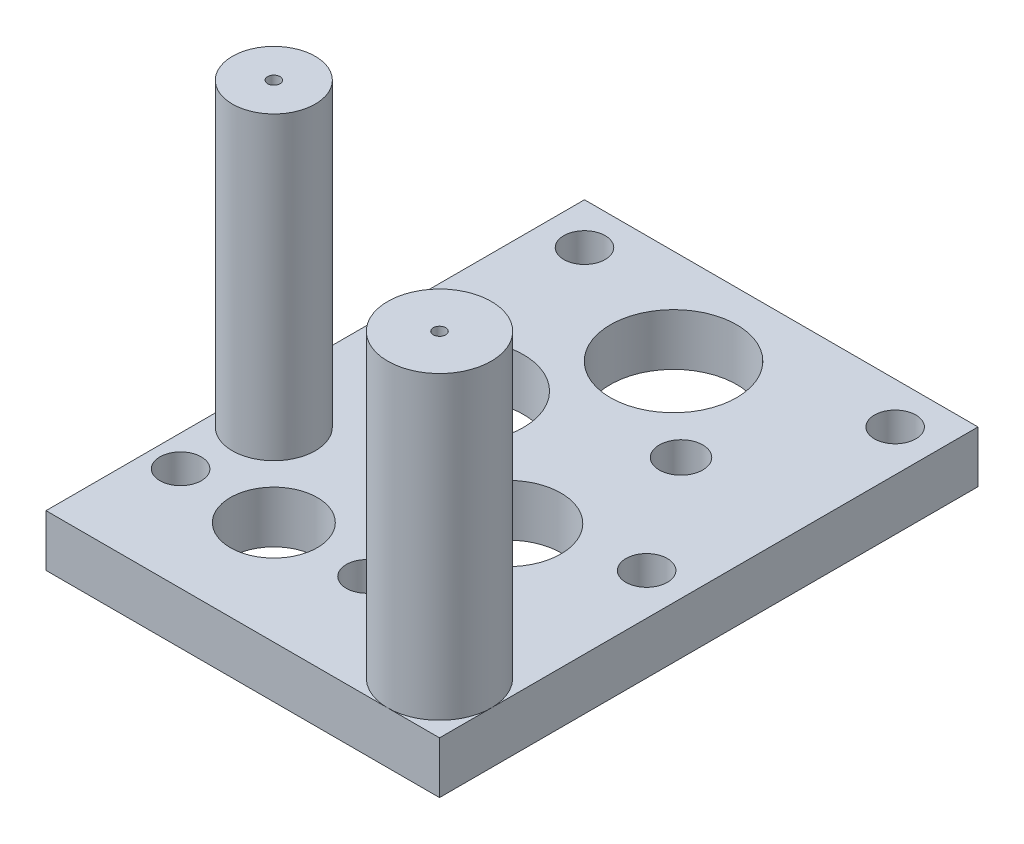
SolidWorks part; units mm, degrees
ref_plane "前视基准面" through (0, 0, 0) normal (0, 0, 1) x (1, 0, 0)
ref_plane "上视基准面" through (0, 0, 0) normal (0, 1, 0) x (1, 0, 0)
ref_plane "右视基准面" through (0, 0, 0) normal (1, 0, 0) x (0, 0, -1)
other "Configuration Table"
sketch "草图1" plane through (0, 0, 0) normal (0, 1, 0) x (1, 0, 0)
  line L1 (-5, 11) -> (14, 11)
  line L2 (-5, 11) -> (-5, -15)
  line L3 (-5, -15) -> (14, -15)
  line L4 (14, 11) -> (14, -15)
  circle A0 centre (0, 0) radius 3.05
  circle A3 centre (8.1071, 2.5542) radius 1.05
  circle A4 centre (3.9, 6.4) radius 3.05
  circle A5 centre (1, -10) radius 2.1
  circle A6 centre (6.6941, -4.3806) radius 2.55
  circle A7 centre (-3.5, -10) radius 1
  circle A8 centre (5.5, -10) radius 1
  circle A10 centre (-3.5, -10) radius 0.8
  circle A11 centre (5.5, -10) radius 0.8
  dimension "D1" = 6.1
  dimension "D2" = 4.2
  dimension "D6" = 2.1
  dimension "D7" = 6.1
  dimension "D17" = 1.6
  dimension "D10" = 5.1
  dimension "D11" = 2
  dimension "D3" = 8
  dimension "D4" = 8
  dimension "D5" = 8.5
  dimension "D8" = 5.7
  dimension "D9" = 6.4
  dimension "D12" = 3.9
  dimension "D13" = 11
  dimension "D14" = 5
  dimension "D15" = 15
  dimension "D16" = 14
extrude "凸台-拉伸1" add sketch "草图1" along normal blind 2.5 contours L4 L3 L2 L1 | A3 | A0 | A4 | A6 | A5
extrude "切除-拉伸2" cut sketch "草图1<3>" against normal blind 1.5 from surface contours A7 | A8 starting at face at (4.5, 2.5, 2)
sketch "草图1<3>" plane through (0, 0, 0) normal (0, 1, 0) x (1, 0, 0) same geometry as "草图1"
extrude "切除-拉伸3" cut sketch "草图1<4>" along normal blind 1.5 contours A10 | A11
sketch "草图1<4>" plane through (0, 0, 0) normal (0, 1, 0) x (1, 0, 0) same geometry as "草图1"
sketch "草图2" plane through (0, 2.5, 0) normal (0, 1, 0) x (1, 0, 0)
  line L0 (-5, -15) -> (14, -15) construction
  line L1 (14, 11) -> (14, -15) construction
  line L2 (-5, 11) -> (-5, -15) construction
  line L3 (-5, 11) -> (14, 11) construction
  circle A0 centre (11.5, -12.5) radius 2.5
  circle A1 centre (-3, -6) radius 2
  circle A2 centre (-3, 9) radius 2
  circle A3 centre (11.5, -12.5) radius 0.3
  circle A4 centre (-3, -6) radius 0.3
  circle A5 centre (-3, 9) radius 0.3
  point P15 (-1.9843, 6.6985)
  dimension "D1" = 5
  dimension "D2" = 0.6
  dimension "D3" = 4
  dimension "D5" = 4
  dimension "D4" = 6
extrude "凸台-拉伸2" add sketch "草图2" along normal blind 14.5 contours A1 | A0
sketch "草图3" plane through (0, 0, -11) normal (0, 0, 1) x (1, 0, 0)
  circle A0 centre (-1, 1.25) radius 0.3
  circle A1 centre (4, 1.25) radius 0.3
  dimension "D1" = 0.6
extrude "切除-拉伸6" cut sketch "草图2<4>" against normal blind 1.5 from surface contours A3 | A4 starting at face at (11.5, 17, 15)
sketch "草图2<4>" plane through (0, 2.5, 0) normal (0, 1, 0) x (1, 0, 0) same geometry as "草图2"
sketch "草图4" plane through (0, 2.5, 0) normal (0, 1, 0) x (1, 0, 0)
  circle A0 centre (12, 9) radius 1
  circle A1 centre (12, 9) radius 0.7
  circle A2 centre (-3, 9) radius 1
  circle A3 centre (-3, 9) radius 0.7
  circle A5 centre (12, -3) radius 1
  circle A6 centre (12, -3) radius 0.7
  point P4 (0, 0)
  point P8 (-3, 9)
  point P10 (0, 0)
  point P11 (0, 0)
  point P12 (0, 0)
  point P14 (0, 0)
  point P17 (0, 0)
  point P18 (0, 0)
  point P20 (0, 0)
  dimension "D1" = 1.4
  dimension "D2" = 2
extrude "切除-拉伸7" cut sketch "草图4" against normal blind 1.5 contours A0 | A2 | A5
extrude "切除-拉伸8" cut sketch "草图4<3>" against normal through all contours A1 | A3 | A6
sketch "草图4<3>" plane through (0, 2.5, 0) normal (0, 1, 0) x (1, 0, 0) same geometry as "草图4"
extrude "切除-拉伸9" cut sketch "草图3" along normal blind 1.5 contours A0 | A1
